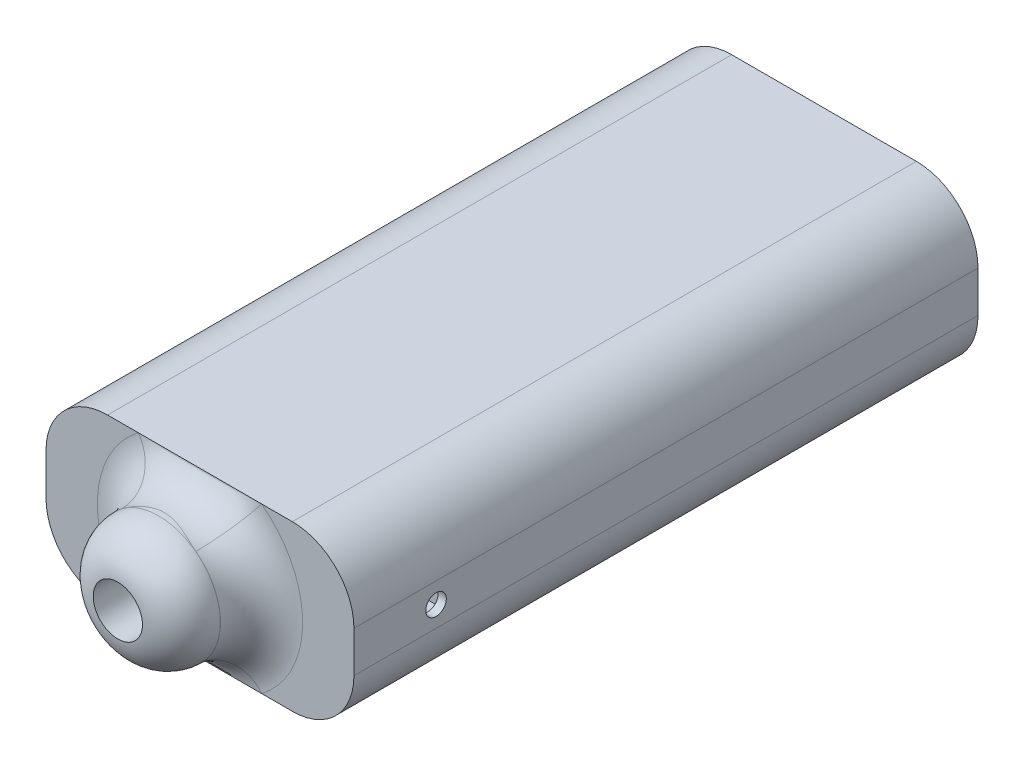
SolidWorks part; units mm, degrees
material "PLA Aero Bambu"
ref_plane "Front Plane" through (0, 0, 0) normal (0, 0, 1) x (1, 0, 0)
ref_plane "Top Plane" through (0, 0, 0) normal (0, 1, 0) x (1, 0, 0)
ref_plane "Right Plane" through (0, 0, 0) normal (1, 0, 0) x (0, 0, -1)
sketch "Sketch1" plane through (0, 0, 0) normal (0, 0, 1) x (1, 0, 0)
  line L1 (-18.75, 10) -> (18.75, 10)
  line L2 (-18.75, 10) -> (-18.75, -10)
  line L3 (-18.75, -10) -> (18.75, -10)
  line L4 (18.75, 10) -> (18.75, -10)
  line L5 (-18.75, 10) -> (18.75, -10) construction
  line L6 (-18.75, -10) -> (18.75, 10) construction
  circle A0 centre (0, 0) radius 2
  point P0 (0, 0)
  dimension "D3" = 4
  dimension "D1" = 20
  dimension "D2" = 37.5
extrude "Boss-Extrude1" add sketch "Sketch1" against normal blind 1
sketch "Sketch2" plane through (0, 0, -1) normal (0, 0, -1) x (-1, 0, 0)
  line L0 (-18.75, 10) -> (-18.75, -10)
  line L1 (18.75, -10) -> (-18.75, -10) construction
  line L2 (-18.75, -10) -> (18.75, -10)
  line L3 (18.75, -10) -> (18.75, 10)
  line L4 (18.75, 10) -> (-18.75, 10)
  line L5 (17.75, 9) -> (-17.75, 9)
  line L6 (-17.75, 9) -> (-17.75, -9)
  line L7 (-17.75, -9) -> (17.75, -9)
  line L8 (17.75, -9) -> (17.75, 9)
  dimension "D1" = 1
extrude "Boss-Extrude2" add sketch "Sketch2" along normal blind 75
fillet "Fillet2" radius 7.5 8 edges at (18.75, 10, -38) (18.75, -10, -38) (-18.75, -10, -38) (-18.75, 10, -38) (-17.75, -9, -38.5) (-17.75, 9, -38.5) (17.75, 9, -38.5) (17.75, -9, -38.5)
sketch "Sketch4" plane through (0, 0, 0) normal (0, 0, 1) x (1, 0, 0)
  circle A0 centre (0, 0) radius 7.5
  circle A1 centre (0, 0) radius 3
  dimension "D1" = 6
  dimension "D2" = 15
extrude "Boss-Extrude3" add sketch "Sketch4" along normal blind 10
fillet "Fillet3" radius 5 2 edges at (7.5, 0, 0) (7.5, 0, 10)
sketch "Sketch6" plane through (0, -9, 0) normal (0, 1, 0) x (1, 0, 0)
  line L0 (-11.25, 76) -> (-11.25, 0) construction
  line L1 (-11.25, 19) -> (11.25, 19)
  line L2 (-11.25, 19) -> (-11.25, 41.45)
  line L3 (-11.25, 41.45) -> (11.25, 41.45)
  line L4 (11.25, 19) -> (11.25, 41.45)
  line L5 (11.25, 0) -> (11.25, 76) construction
  line L9 (10.25, 1) -> (-10.25, 1) construction
  dimension "D1" = 18
  dimension "D2" = 22.45
extrude "Boss-Extrude4" add sketch "Sketch6" along normal blind 2.9
sketch "Sketch7" plane through (0, 9, 0) normal (0, -1, 0) x (1, 0, 0)
  line L0 (11.25, 0) -> (11.25, -76) construction
  line L1 (11.25, -19) -> (-11.25, -19)
  line L2 (11.25, -19) -> (11.25, -41.45)
  line L3 (11.25, -41.45) -> (-11.25, -41.45)
  line L4 (-11.25, -19) -> (-11.25, -41.45)
  line L5 (-11.25, -76) -> (-11.25, 0) construction
  line L6 (11.25, -41.45) -> (-11.25, -41.45) construction
  line L7 (-11.25, -19) -> (11.25, -19) construction
extrude "Boss-Extrude5" add sketch "Sketch7" along normal blind 3
sketch "Sketch8" plane through (-17.75, 0, 0) normal (1, 0, 0) x (0, 0, -1)
  line L0 (76, 1.5) -> (1, 1.5) construction
  line L1 (19, 1.5) -> (38.5, 1.5)
  line L2 (19, 1.5) -> (19, -1.5)
  line L3 (19, -1.5) -> (38.5, -1.5)
  line L4 (38.5, 1.5) -> (38.5, -1.5)
  line L5 (1, -1.5) -> (76, -1.5) construction
  line L6 (1, -1.5) -> (1, 1.5) construction
  dimension "D1" = 18
extrude "Boss-Extrude6" add sketch "Sketch8" along normal blind 2.5
sketch "Sketch9" plane through (0, 0, -1) normal (0, 0, -1) x (-1, 0, 0)
  line L0 (11.25, 6) -> (-11.25, 6) construction
  line L1 (-5.75, 4) -> (-3.25, 4)
  line L2 (-5.75, 4) -> (-5.75, -4.1)
  line L3 (-5.75, -4.1) -> (-3.25, -4.1)
  line L4 (-3.25, 4) -> (-3.25, -4.1)
  line L5 (-11.25, -6.1) -> (11.25, -6.1) construction
  line L6 (-17.75, 1.5) -> (-17.75, -1.5) construction
  dimension "D1" = 2
  dimension "D2" = 2
  dimension "D3" = 12
  dimension "D4" = 2.5
extrude "Boss-Extrude7" add sketch "Sketch9" along normal blind 6.5
sketch "Sketch5" plane through (18.75, 0, 0) normal (1, 0, 0) x (0, 0, -1)
  circle A0 centre (10, 0) radius 1.25
  dimension "D1" = 2.5
  dimension "D2" = 10
extrude "Cut-Extrude1" cut sketch "Sketch5" against normal through all
